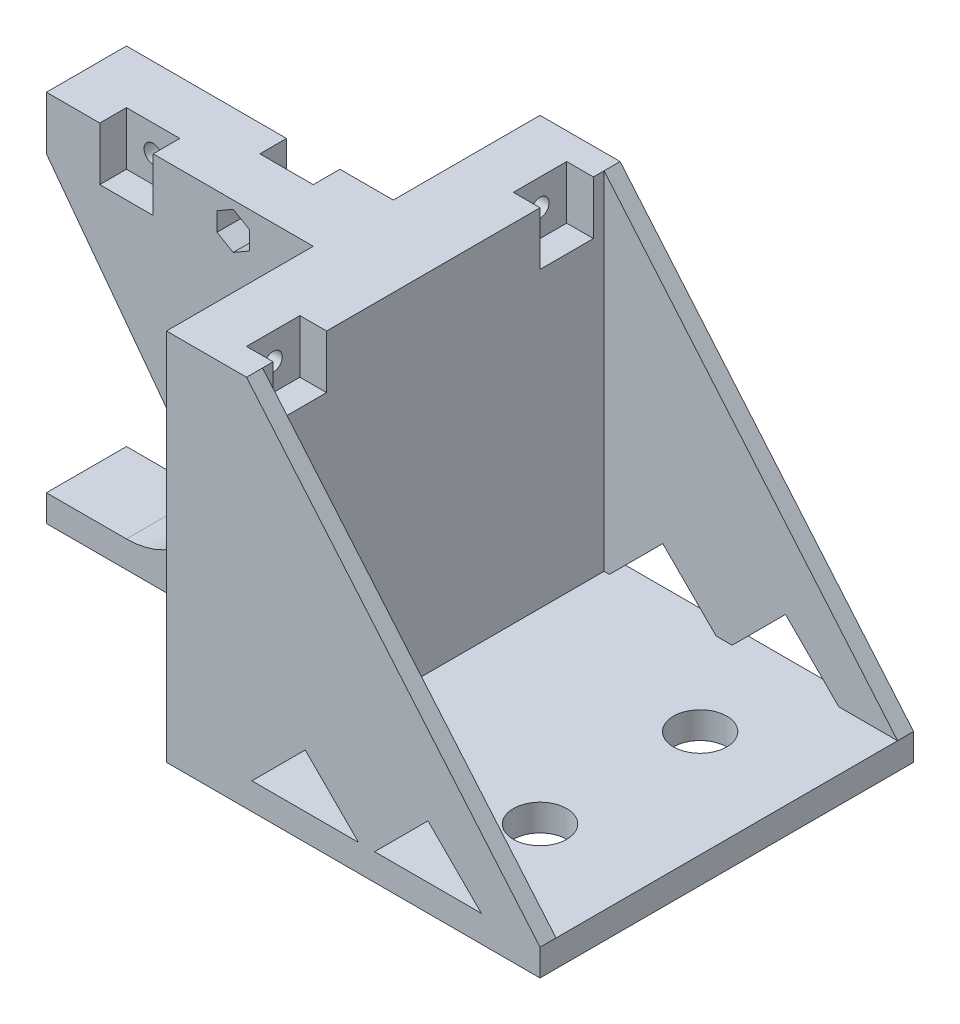
SolidWorks part; units mm, degrees
ref_plane "前视基准面" through (0, 0, 0) normal (0, 0, 1) x (1, 0, 0)
ref_plane "上视基准面" through (0, 0, 0) normal (0, 1, 0) x (1, 0, 0)
ref_plane "右视基准面" through (0, 0, 0) normal (1, 0, 0) x (0, 0, -1)
sketch "Sketch1" plane through (0, 0, 0) normal (0, 1, 0) x (1, 0, 0)
  line L0 (-60, 0) -> (-10, 0) construction
  line L1 (-60, -35) -> (60, -35) construction
  line L2 (-60, -35) -> (-60, 35) construction
  line L3 (-60, 35) -> (60, 35) construction
  line L4 (60, -35) -> (60, 35)
  line L5 (-60, -35) -> (60, 35) construction
  line L6 (-60, 35) -> (60, -35) construction
  line L7 (-10, 35) -> (-10, -35) construction
  line L8 (-60, 7.5) -> (-10, 7.5)
  line L9 (-60, -7.5) -> (-10, -7.5)
  line L10 (-60, 7.5) -> (-60, -7.5)
  line L11 (-10, 0) -> (60, 0) construction
  line L12 (40, 15) -> (40, -15) construction
  line L13 (-10, 7.5) -> (-10, 35)
  line L14 (-10, 35) -> (60, 35)
  line L20 (60, -35) -> (-10, -35)
  line L21 (-10, -35) -> (-10, -7.5)
  circle A0 centre (40, 15) radius 5
  circle A1 centre (40, -15) radius 5
  point P0 (0, 0)
  point P17 (40, 0)
  dimension "D6" = 10
  dimension "D1" = 50
  dimension "D2" = 70
  dimension "D3" = 15
  dimension "D4" = 70
  dimension "D5" = 20
  dimension "D7" = 30
extrude "Boss-Extrude1" add sketch "Sketch1" along normal blind 5
sketch "Sketch2" plane through (0, 5, 0) normal (0, 1, 0) x (1, 0, 0)
  line L0 (-10, 35) -> (-10, 7.5)
  line L1 (-10, 35) -> (5, 35)
  line L2 (60, 35) -> (-10, 35) construction
  line L4 (5, 35) -> (5, -35)
  line L5 (-10, -35) -> (60, -35) construction
  line L6 (5, -35) -> (-10, -35)
  line L9 (-10, 7.5) -> (-30, 7.5)
  line L10 (-10, 7.5) -> (-60, 7.5) construction
  line L11 (-30, 7.5) -> (-30, -7.5)
  line L12 (-60, -7.5) -> (-10, -7.5) construction
  line L13 (-30, -7.5) -> (-10, -7.5)
  line L14 (-10, -7.5) -> (-10, -35)
  dimension "D1" = 15
  dimension "D3" = 20
extrude "Boss-Extrude2" add sketch "Sketch2" along normal blind 65
sketch "Sketch3" plane through (-30, 0, 0) normal (-1, 0, 0) x (0, 0, 1)
  line L0 (7.5, 70) -> (7.5, 0) construction
  line L1 (-7.5, 70) -> (7.5, 70)
  line L2 (-7.5, 70) -> (-7.5, 60)
  line L3 (-7.5, 60) -> (7.5, 60)
  line L4 (7.5, 70) -> (7.5, 60)
  dimension "D1" = 10
extrude "Boss-Extrude3" add sketch "Sketch3" along normal blind 30
chamfer "Chamfer2" distance 40 distance2 30 1 edges at (-30, 60, 0) first distance on face at (-30, 46.25, -1.875)
sketch "Sketch4" plane through (0, 70, 0) normal (0, 1, 0) x (1, 0, 0)
  line L0 (-20, 7.5) -> (-20, 2.5)
  line L1 (-10, 7.5) -> (-60, 7.5) construction
  line L2 (-20, 2.5) -> (-30, 2.5)
  line L3 (-30, 2.5) -> (-30, 7.5)
  line L4 (-30, 7.5) -> (-20, 7.5)
  line L6 (-40, -2.5) -> (-40, -7.5)
  line L7 (-40, -7.5) -> (-50, -7.5)
  line L8 (-50, -7.5) -> (-50, -2.5)
  line L9 (-50, -2.5) -> (-40, -2.5)
  line L10 (-60, -7.5) -> (-10, -7.5) construction
  line L12 (5, 30) -> (0, 30)
  line L13 (5, 30) -> (5, 20)
  line L14 (5, 20) -> (0, 20)
  line L15 (0, 30) -> (0, 20)
  line L16 (5, 20) -> (5, -20) construction
  line L17 (5, -20) -> (0, -20)
  line L18 (5, -20) -> (5, -30)
  line L19 (5, -30) -> (0, -30)
  line L20 (0, -20) -> (0, -30)
  line L22 (5, -35) -> (5, 35) construction
  point P24 (5, 0)
  dimension "D1" = 25
  dimension "D2" = 10
  dimension "D3" = 5
  dimension "D4" = 10
  dimension "D5" = 10
  dimension "D6" = 5
  dimension "D7" = 10
  dimension "D8" = 40
extrude "Cut-Extrude1" cut sketch "Sketch4" against normal blind 10
sketch "Sketch5" plane through (0, 0, 0) normal (1, 0, 0) x (0, 0, -1)
  line L0 (-30, 70) -> (-20, 60) construction
  line L1 (-30, 70) -> (-20, 70) construction
  line L2 (-30, 70) -> (-30, 60) construction
  line L3 (-30, 60) -> (-20, 60) construction
  line L4 (-20, 70) -> (-20, 60) construction
  line L5 (-20, 70) -> (-30, 60) construction
  line L7 (-25, 61.5) -> (-21.9689, 63.25)
  line L8 (-21.9689, 63.25) -> (-21.9689, 66.75)
  line L9 (-21.9689, 66.75) -> (-25, 68.5)
  line L10 (-25, 68.5) -> (-28.0311, 66.75)
  line L11 (-28.0311, 66.75) -> (-28.0311, 63.25)
  line L12 (-28.0311, 63.25) -> (-25, 61.5)
  circle A0 centre (-25, 65) radius 3.0311 construction
  dimension "D1" = 3.5
extrude "Cut-Extrude2" cut sketch "Sketch5" against normal blind 10 from offset 5 offset against normal yes
sketch "Sketch6" plane through (0, 0, 0) normal (1, 0, 0) x (0, 0, -1)
  line L0 (-30, 70) -> (-20, 60) construction
  line L1 (-20, 60) -> (-20, 70) construction
  line L2 (-20, 70) -> (-28.499, 61.501) construction
  circle A0 centre (-25, 65) radius 1.7
  dimension "D1" = 3.4
extrude "Cut-Extrude3" cut sketch "Sketch6" against normal blind 10
mirror "Mirror1" about plane through (0, 0, 0) normal (0, 0, 1) of "Cut-Extrude2"
mirror "Mirror2" about plane through (0, 0, 0) normal (0, 0, 1) of "Cut-Extrude3"
sketch "Sketch7" plane through (0, 0, 2.5) normal (0, 0, 1) x (1, 0, 0)
  line L0 (-50, 70) -> (-40, 60) construction
  line L1 (-40, 60) -> (-40, 70) construction
  line L2 (-40, 70) -> (-50, 60) construction
  circle A0 centre (-45, 65) radius 1.7
  dimension "D1" = 3.4
extrude "Cut-Extrude4" cut sketch "Sketch7" against normal blind 10
sketch "Sketch8" plane through (0, 0, 2.5) normal (0, 0, 1) x (1, 0, 0)
  line L0 (-50, 60) -> (-50, 70) construction
  line L1 (-45, 68.5) -> (-48.0311, 66.75)
  line L2 (-48.0311, 66.75) -> (-48.0311, 63.25)
  line L3 (-48.0311, 63.25) -> (-45, 61.5)
  line L4 (-45, 61.5) -> (-41.9689, 63.25)
  line L5 (-41.9689, 63.25) -> (-41.9689, 66.75)
  line L6 (-41.9689, 66.75) -> (-45, 68.5)
  circle A0 centre (-45, 65) radius 3.0311 construction
  dimension "D1" = 3.5
extrude "Cut-Extrude5" cut sketch "Sketch8" against normal blind 10 from offset 5 offset against normal yes
sketch "Sketch9" plane through (0, 0, -2.5) normal (0, 0, -1) x (-1, 0, 0)
  line L0 (20, 70) -> (30, 60) construction
  line L1 (30, 60) -> (30, 70) construction
  line L2 (30, 70) -> (20, 60) construction
  circle A0 centre (25, 65) radius 1.7
  dimension "D1" = 3.4
extrude "Cut-Extrude6" cut sketch "Sketch9" against normal blind 10
sketch "Sketch10" plane through (0, 0, -2.5) normal (0, 0, -1) x (-1, 0, 0)
  line L0 (20, 60) -> (20, 70) construction
  line L1 (25, 68.5) -> (21.9689, 66.75)
  line L2 (21.9689, 66.75) -> (21.9689, 63.25)
  line L3 (21.9689, 63.25) -> (25, 61.5)
  line L4 (25, 61.5) -> (28.0311, 63.25)
  line L5 (28.0311, 63.25) -> (28.0311, 66.75)
  line L6 (28.0311, 66.75) -> (25, 68.5)
  circle A0 centre (25, 65) radius 3.0311 construction
  dimension "D1" = 3.5
extrude "Cut-Extrude7" cut sketch "Sketch10" against normal blind 10 from offset 5 offset against normal yes
fillet "Fillet2" radius 15 1 edges
sketch "Sketch11" plane through (0, 0, -35) normal (0, 0, -1) x (-1, 0, 0)
  line L0 (-5, 70) -> (-60, 5)
  line L1 (-60, 5) -> (-49, 5)
  line L2 (-5, 5) -> (-5, 70)
  line L3 (-6, 5) -> (-16, 15)
  line L4 (-16, 15) -> (-26, 5)
  line L5 (-29, 5) -> (-39, 15)
  line L6 (-39, 15) -> (-49, 5)
  line L7 (-29, 5) -> (-26, 5)
  line L8 (-6, 5) -> (-5, 5)
  dimension "D1" = 3
  dimension "D2" = 1
  dimension "D3" = 20
extrude "Boss-Extrude4" add sketch "Sketch11" against normal blind 3
mirror "Mirror3" about plane through (0, 0, 0) normal (0, 0, 1) of "Boss-Extrude4"
